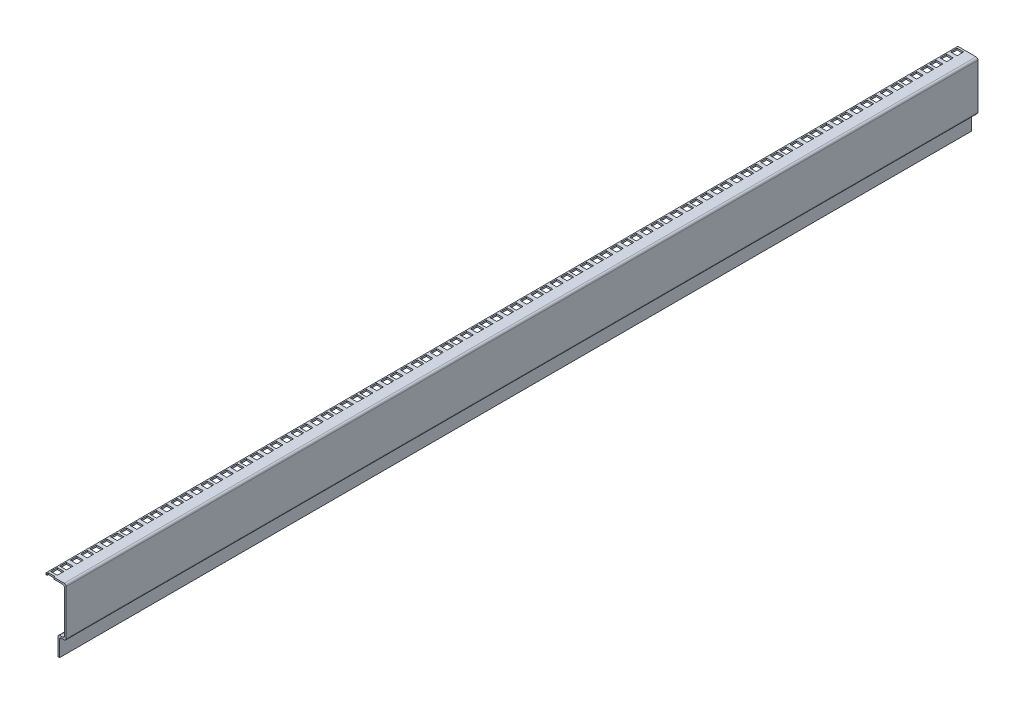
SolidWorks part; units mm, degrees
ref_plane "Front Plane" through (0, 0, 0) normal (0, 0, 1) x (1, 0, 0)
ref_plane "Top Plane" through (0, 0, 0) normal (0, 1, 0) x (1, 0, 0)
ref_plane "Right Plane" through (0, 0, 0) normal (1, 0, 0) x (0, 0, -1)
ref_plane "Plane1" through (-6.8, 0, 0) normal (-1, 0, 0) x (0, -1, 0)
sketch "Sketch1" plane through (-6.8, 0, 0) normal (-1, 0, 0) x (0, -1, 0)
  line L0 (-2.5, -935) -> (99, -935)
  line L1 (99, -935) -> (99, 450.86)
  line L2 (99, 450.86) -> (-2.5, 450.86)
  line L3 (-2.5, 450.86) -> (-2.5, -935)
  dimension "D1" = 101.5
  dimension "D2" = 1385.86
extrude "Boss-Extrude1" add sketch "Sketch1" against normal blind 30.6
sketch "Sketch2" plane through (0, 0, -935) normal (0, 0, -1) x (-1, 0, 0)
  line L0 (6.8, -99) -> (6.8, 0)
  line L1 (6.8, 0) -> (-21.3, 0)
  line L2 (-21.3, 0) -> (-21.3, -99)
  line L3 (-21.3, -99) -> (6.8, -99)
  line L4 (-23.8, 2.5) -> (-23.8, -99) construction
  line L5 (-23.8, 2.5) -> (6.8, 2.5) construction
  line L6 (6.8, 2.5) -> (6.8, -99) construction
  line L7 (-23.8, -99) -> (6.8, -99) construction
  dimension "D1" = 2.5
  dimension "D2" = 2.5
extrude "Cut-Extrude1" cut sketch "Sketch2" against normal through all
sketch "Sketch3" plane through (21.3, 0, 0) normal (-1, 0, 0) x (0, 0, 1)
  line L0 (-935, -99) -> (-935, -69.5)
  line L1 (-935, -69.5) -> (450.86, -69.5)
  line L2 (450.86, -69.5) -> (450.86, -99)
  line L3 (450.86, -99) -> (-935, -99)
  line L4 (-935, 0) -> (-935, -99) construction
  line L5 (450.86, 0) -> (450.86, -99) construction
  line L6 (450.86, -99) -> (-935, -99) construction
  dimension "D1" = 29.5
extrude "Boss-Extrude2" add sketch "Sketch3" along normal blind 10
sketch "Sketch4" plane through (0, 0, 450.86) normal (0, 0, 1) x (1, 0, 0)
  line L0 (23.8, -72) -> (13.8, -72)
  line L1 (13.8, -72) -> (13.8, -99)
  line L2 (13.8, -99) -> (23.8, -99)
  line L3 (23.8, -99) -> (23.8, -72)
  line L4 (11.3, -69.5) -> (21.3, -69.5) construction
  line L5 (11.3, -99) -> (11.3, -69.5) construction
  line L6 (23.8, -99) -> (23.8, 2.5) construction
  line L7 (23.8, -99) -> (11.3, -99) construction
  dimension "D1" = 2.5
  dimension "D2" = 2.5
extrude "Cut-Extrude2" cut sketch "Sketch4" against normal through all
sketch "Sketch5" plane through (0, 2.5, 0) normal (0, 1, 0) x (-1, 0, 0)
  line L0 (-5, 923.15) -> (5, 923.15)
  line L1 (5, 923.15) -> (5, 449.01)
  line L2 (5, 449.01) -> (-5, 449.01)
  line L3 (-5, 449.01) -> (-5, 923.15)
  line L4 (-23.8, 450.86) -> (6.8, 450.86) construction
  line L5 (6.8, 450.86) -> (6.8, -935) construction
  dimension "D1" = 1.85
  dimension "D2" = 1.8
extrude "Cut-Extrude3" cut sketch "Sketch5" against normal through all
sketch "Sketch37" plane through (0, 2.5, 0) normal (0, 1, 0) x (-1, 0, 0)
  line L0 (-5, 435.5463) -> (5, 435.5463)
  line L1 (5, 435.5463) -> (5, 445.5463)
  line L2 (5, 445.5463) -> (-5, 445.5463)
  line L3 (-5, 445.5463) -> (-5, 435.5463)
extrude "Cut-Extrude35" cut sketch "Sketch37" against normal through all
sketch "Sketch38" plane through (0, 2.5, 0) normal (0, 1, 0) x (-1, 0, 0)
  line L0 (-5, 421.711) -> (5, 421.711)
  line L1 (5, 421.711) -> (5, 431.711)
  line L2 (5, 431.711) -> (-5, 431.711)
  line L3 (-5, 431.711) -> (-5, 421.711)
extrude "Cut-Extrude36" cut sketch "Sketch38" against normal through all
sketch "Sketch39" plane through (0, 2.5, 0) normal (0, 1, 0) x (-1, 0, 0)
  line L0 (-5, 405.836) -> (5, 405.836)
  line L1 (5, 405.836) -> (5, 415.836)
  line L2 (5, 415.836) -> (-5, 415.836)
  line L3 (-5, 415.836) -> (-5, 405.836)
extrude "Cut-Extrude37" cut sketch "Sketch39" against normal through all
sketch "Sketch40" plane through (0, 2.5, 0) normal (0, 1, 0) x (-1, 0, 0)
  line L0 (-5, 389.961) -> (5, 389.961)
  line L1 (5, 389.961) -> (5, 399.961)
  line L2 (5, 399.961) -> (-5, 399.961)
  line L3 (-5, 399.961) -> (-5, 389.961)
extrude "Cut-Extrude38" cut sketch "Sketch40" against normal through all
sketch "Sketch41" plane through (0, 2.5, 0) normal (0, 1, 0) x (-1, 0, 0)
  line L0 (-5, 376.1256) -> (5, 376.1256)
  line L1 (5, 376.1256) -> (5, 386.1256)
  line L2 (5, 386.1256) -> (-5, 386.1256)
  line L3 (-5, 386.1256) -> (-5, 376.1256)
extrude "Cut-Extrude39" cut sketch "Sketch41" against normal through all
sketch "Sketch42" plane through (0, 2.5, 0) normal (0, 1, 0) x (-1, 0, 0)
  line L0 (-5, 360.2506) -> (5, 360.2506)
  line L1 (5, 360.2506) -> (5, 370.2506)
  line L2 (5, 370.2506) -> (-5, 370.2506)
  line L3 (-5, 370.2506) -> (-5, 360.2506)
extrude "Cut-Extrude40" cut sketch "Sketch42" against normal through all
sketch "Sketch43" plane through (0, 2.5, 0) normal (0, 1, 0) x (-1, 0, 0)
  line L0 (-5, 344.3756) -> (5, 344.3756)
  line L1 (5, 344.3756) -> (5, 354.3756)
  line L2 (5, 354.3756) -> (-5, 354.3756)
  line L3 (-5, 354.3756) -> (-5, 344.3756)
extrude "Cut-Extrude41" cut sketch "Sketch43" against normal through all
sketch "Sketch44" plane through (0, 2.5, 0) normal (0, 1, 0) x (-1, 0, 0)
  line L0 (-5, 330.5402) -> (5, 330.5402)
  line L1 (5, 330.5402) -> (5, 340.5402)
  line L2 (5, 340.5402) -> (-5, 340.5402)
  line L3 (-5, 340.5402) -> (-5, 330.5402)
extrude "Cut-Extrude42" cut sketch "Sketch44" against normal through all
sketch "Sketch45" plane through (0, 2.5, 0) normal (0, 1, 0) x (-1, 0, 0)
  line L0 (-5, 314.6652) -> (5, 314.6652)
  line L1 (5, 314.6652) -> (5, 324.6652)
  line L2 (5, 324.6652) -> (-5, 324.6652)
  line L3 (-5, 324.6652) -> (-5, 314.6652)
extrude "Cut-Extrude43" cut sketch "Sketch45" against normal through all
sketch "Sketch46" plane through (0, 2.5, 0) normal (0, 1, 0) x (-1, 0, 0)
  line L0 (-5, 298.7902) -> (5, 298.7902)
  line L1 (5, 298.7902) -> (5, 308.7902)
  line L2 (5, 308.7902) -> (-5, 308.7902)
  line L3 (-5, 308.7902) -> (-5, 298.7902)
extrude "Cut-Extrude44" cut sketch "Sketch46" against normal through all
sketch "Sketch47" plane through (0, 2.5, 0) normal (0, 1, 0) x (-1, 0, 0)
  line L0 (-5, 284.9549) -> (5, 284.9549)
  line L1 (5, 284.9549) -> (5, 294.9549)
  line L2 (5, 294.9549) -> (-5, 294.9549)
  line L3 (-5, 294.9549) -> (-5, 284.9549)
extrude "Cut-Extrude45" cut sketch "Sketch47" against normal through all
sketch "Sketch48" plane through (0, 2.5, 0) normal (0, 1, 0) x (-1, 0, 0)
  line L0 (-5, 269.0799) -> (5, 269.0799)
  line L1 (5, 269.0799) -> (5, 279.0799)
  line L2 (5, 279.0799) -> (-5, 279.0799)
  line L3 (-5, 279.0799) -> (-5, 269.0799)
extrude "Cut-Extrude46" cut sketch "Sketch48" against normal through all
sketch "Sketch49" plane through (0, 2.5, 0) normal (0, 1, 0) x (-1, 0, 0)
  line L0 (-5, 253.2049) -> (5, 253.2049)
  line L1 (5, 253.2049) -> (5, 263.2049)
  line L2 (5, 263.2049) -> (-5, 263.2049)
  line L3 (-5, 263.2049) -> (-5, 253.2049)
extrude "Cut-Extrude47" cut sketch "Sketch49" against normal through all
sketch "Sketch50" plane through (0, 2.5, 0) normal (0, 1, 0) x (-1, 0, 0)
  line L0 (-5, 239.3695) -> (5, 239.3695)
  line L1 (5, 239.3695) -> (5, 249.3695)
  line L2 (5, 249.3695) -> (-5, 249.3695)
  line L3 (-5, 249.3695) -> (-5, 239.3695)
extrude "Cut-Extrude48" cut sketch "Sketch50" against normal through all
sketch "Sketch51" plane through (0, 2.5, 0) normal (0, 1, 0) x (-1, 0, 0)
  line L0 (-5, 223.4945) -> (5, 223.4945)
  line L1 (5, 223.4945) -> (5, 233.4945)
  line L2 (5, 233.4945) -> (-5, 233.4945)
  line L3 (-5, 233.4945) -> (-5, 223.4945)
extrude "Cut-Extrude49" cut sketch "Sketch51" against normal through all
sketch "Sketch52" plane through (0, 2.5, 0) normal (0, 1, 0) x (-1, 0, 0)
  line L0 (-5, 207.6195) -> (5, 207.6195)
  line L1 (5, 207.6195) -> (5, 217.6195)
  line L2 (5, 217.6195) -> (-5, 217.6195)
  line L3 (-5, 217.6195) -> (-5, 207.6195)
extrude "Cut-Extrude50" cut sketch "Sketch52" against normal through all
sketch "Sketch53" plane through (0, 2.5, 0) normal (0, 1, 0) x (-1, 0, 0)
  line L0 (-5, 193.7841) -> (5, 193.7841)
  line L1 (5, 193.7841) -> (5, 203.7841)
  line L2 (5, 203.7841) -> (-5, 203.7841)
  line L3 (-5, 203.7841) -> (-5, 193.7841)
extrude "Cut-Extrude51" cut sketch "Sketch53" against normal through all
sketch "Sketch54" plane through (0, 2.5, 0) normal (0, 1, 0) x (-1, 0, 0)
  line L0 (-5, 177.9091) -> (5, 177.9091)
  line L1 (5, 177.9091) -> (5, 187.9091)
  line L2 (5, 187.9091) -> (-5, 187.9091)
  line L3 (-5, 187.9091) -> (-5, 177.9091)
extrude "Cut-Extrude52" cut sketch "Sketch54" against normal through all
sketch "Sketch55" plane through (0, 2.5, 0) normal (0, 1, 0) x (-1, 0, 0)
  line L0 (-5, 162.0341) -> (5, 162.0341)
  line L1 (5, 162.0341) -> (5, 172.0341)
  line L2 (5, 172.0341) -> (-5, 172.0341)
  line L3 (-5, 172.0341) -> (-5, 162.0341)
extrude "Cut-Extrude53" cut sketch "Sketch55" against normal through all
sketch "Sketch56" plane through (0, 2.5, 0) normal (0, 1, 0) x (-1, 0, 0)
  line L0 (-5, 148.1988) -> (5, 148.1988)
  line L1 (5, 148.1988) -> (5, 158.1988)
  line L2 (5, 158.1988) -> (-5, 158.1988)
  line L3 (-5, 158.1988) -> (-5, 148.1988)
extrude "Cut-Extrude54" cut sketch "Sketch56" against normal through all
sketch "Sketch57" plane through (0, 2.5, 0) normal (0, 1, 0) x (-1, 0, 0)
  line L0 (-5, 132.3238) -> (5, 132.3238)
  line L1 (5, 132.3238) -> (5, 142.3238)
  line L2 (5, 142.3238) -> (-5, 142.3238)
  line L3 (-5, 142.3238) -> (-5, 132.3238)
extrude "Cut-Extrude55" cut sketch "Sketch57" against normal through all
sketch "Sketch58" plane through (0, 2.5, 0) normal (0, 1, 0) x (-1, 0, 0)
  line L0 (-5, 116.4488) -> (5, 116.4488)
  line L1 (5, 116.4488) -> (5, 126.4488)
  line L2 (5, 126.4488) -> (-5, 126.4488)
  line L3 (-5, 126.4488) -> (-5, 116.4488)
extrude "Cut-Extrude56" cut sketch "Sketch58" against normal through all
sketch "Sketch59" plane through (0, 2.5, 0) normal (0, 1, 0) x (-1, 0, 0)
  line L0 (-5, 102.6134) -> (5, 102.6134)
  line L1 (5, 102.6134) -> (5, 112.6134)
  line L2 (5, 112.6134) -> (-5, 112.6134)
  line L3 (-5, 112.6134) -> (-5, 102.6134)
extrude "Cut-Extrude57" cut sketch "Sketch59" against normal through all
sketch "Sketch60" plane through (0, 2.5, 0) normal (0, 1, 0) x (-1, 0, 0)
  line L0 (-5, 86.7384) -> (5, 86.7384)
  line L1 (5, 86.7384) -> (5, 96.7384)
  line L2 (5, 96.7384) -> (-5, 96.7384)
  line L3 (-5, 96.7384) -> (-5, 86.7384)
extrude "Cut-Extrude58" cut sketch "Sketch60" against normal through all
sketch "Sketch61" plane through (0, 2.5, 0) normal (0, 1, 0) x (-1, 0, 0)
  line L0 (-5, 70.8634) -> (5, 70.8634)
  line L1 (5, 70.8634) -> (5, 80.8634)
  line L2 (5, 80.8634) -> (-5, 80.8634)
  line L3 (-5, 80.8634) -> (-5, 70.8634)
extrude "Cut-Extrude59" cut sketch "Sketch61" against normal through all
sketch "Sketch62" plane through (0, 2.5, 0) normal (0, 1, 0) x (-1, 0, 0)
  line L0 (-5, 57.028) -> (5, 57.028)
  line L1 (5, 57.028) -> (5, 67.028)
  line L2 (5, 67.028) -> (-5, 67.028)
  line L3 (-5, 67.028) -> (-5, 57.028)
extrude "Cut-Extrude60" cut sketch "Sketch62" against normal through all
sketch "Sketch63" plane through (0, 2.5, 0) normal (0, 1, 0) x (-1, 0, 0)
  line L0 (-5, 41.153) -> (5, 41.153)
  line L1 (5, 41.153) -> (5, 51.153)
  line L2 (5, 51.153) -> (-5, 51.153)
  line L3 (-5, 51.153) -> (-5, 41.153)
extrude "Cut-Extrude61" cut sketch "Sketch63" against normal through all
sketch "Sketch64" plane through (0, 2.5, 0) normal (0, 1, 0) x (-1, 0, 0)
  line L0 (-5, 25.278) -> (5, 25.278)
  line L1 (5, 25.278) -> (5, 35.278)
  line L2 (5, 35.278) -> (-5, 35.278)
  line L3 (-5, 35.278) -> (-5, 25.278)
extrude "Cut-Extrude62" cut sketch "Sketch64" against normal through all
sketch "Sketch65" plane through (0, 2.5, 0) normal (0, 1, 0) x (-1, 0, 0)
  line L0 (-5, 11.4427) -> (5, 11.4427)
  line L1 (5, 11.4427) -> (5, 21.4427)
  line L2 (5, 21.4427) -> (-5, 21.4427)
  line L3 (-5, 21.4427) -> (-5, 11.4427)
extrude "Cut-Extrude63" cut sketch "Sketch65" against normal through all
sketch "Sketch66" plane through (0, 2.5, 0) normal (0, 1, 0) x (-1, 0, 0)
  line L0 (-5, -4.4323) -> (5, -4.4323)
  line L1 (5, -4.4323) -> (5, 5.5677)
  line L2 (5, 5.5677) -> (-5, 5.5677)
  line L3 (-5, 5.5677) -> (-5, -4.4323)
extrude "Cut-Extrude64" cut sketch "Sketch66" against normal through all
sketch "Sketch67" plane through (0, 2.5, 0) normal (0, 1, 0) x (-1, 0, 0)
  line L0 (-5, -34.1427) -> (5, -34.1427)
  line L1 (5, -34.1427) -> (5, -24.1427)
  line L2 (5, -24.1427) -> (-5, -24.1427)
  line L3 (-5, -24.1427) -> (-5, -34.1427)
extrude "Cut-Extrude65" cut sketch "Sketch67" against normal through all
sketch "Sketch68" plane through (0, 2.5, 0) normal (0, 1, 0) x (-1, 0, 0)
  line L0 (-5, -50.0177) -> (5, -50.0177)
  line L1 (5, -50.0177) -> (5, -40.0177)
  line L2 (5, -40.0177) -> (-5, -40.0177)
  line L3 (-5, -40.0177) -> (-5, -50.0177)
extrude "Cut-Extrude66" cut sketch "Sketch68" against normal through all
sketch "Sketch69" plane through (0, 2.5, 0) normal (0, 1, 0) x (-1, 0, 0)
  line L0 (-5, -65.8927) -> (5, -65.8927)
  line L1 (5, -65.8927) -> (5, -55.8927)
  line L2 (5, -55.8927) -> (-5, -55.8927)
  line L3 (-5, -55.8927) -> (-5, -65.8927)
extrude "Cut-Extrude67" cut sketch "Sketch69" against normal through all
sketch "Sketch70" plane through (0, 2.5, 0) normal (0, 1, 0) x (-1, 0, 0)
  line L0 (-5, -79.728) -> (5, -79.728)
  line L1 (5, -79.728) -> (5, -69.728)
  line L2 (5, -69.728) -> (-5, -69.728)
  line L3 (-5, -69.728) -> (-5, -79.728)
extrude "Cut-Extrude68" cut sketch "Sketch70" against normal through all
sketch "Sketch71" plane through (0, 2.5, 0) normal (0, 1, 0) x (-1, 0, 0)
  line L0 (-5, -95.603) -> (5, -95.603)
  line L1 (5, -95.603) -> (5, -85.603)
  line L2 (5, -85.603) -> (-5, -85.603)
  line L3 (-5, -85.603) -> (-5, -95.603)
extrude "Cut-Extrude69" cut sketch "Sketch71" against normal through all
sketch "Sketch72" plane through (0, 2.5, 0) normal (0, 1, 0) x (-1, 0, 0)
  line L0 (-5, -111.478) -> (5, -111.478)
  line L1 (5, -111.478) -> (5, -101.478)
  line L2 (5, -101.478) -> (-5, -101.478)
  line L3 (-5, -101.478) -> (-5, -111.478)
extrude "Cut-Extrude70" cut sketch "Sketch72" against normal through all
sketch "Sketch73" plane through (0, 2.5, 0) normal (0, 1, 0) x (-1, 0, 0)
  line L0 (-5, -125.3134) -> (5, -125.3134)
  line L1 (5, -125.3134) -> (5, -115.3134)
  line L2 (5, -115.3134) -> (-5, -115.3134)
  line L3 (-5, -115.3134) -> (-5, -125.3134)
extrude "Cut-Extrude71" cut sketch "Sketch73" against normal through all
sketch "Sketch74" plane through (0, 2.5, 0) normal (0, 1, 0) x (-1, 0, 0)
  line L0 (-5, -141.1884) -> (5, -141.1884)
  line L1 (5, -141.1884) -> (5, -131.1884)
  line L2 (5, -131.1884) -> (-5, -131.1884)
  line L3 (-5, -131.1884) -> (-5, -141.1884)
extrude "Cut-Extrude72" cut sketch "Sketch74" against normal through all
sketch "Sketch75" plane through (0, 2.5, 0) normal (0, 1, 0) x (-1, 0, 0)
  line L0 (-5, -157.0634) -> (5, -157.0634)
  line L1 (5, -157.0634) -> (5, -147.0634)
  line L2 (5, -147.0634) -> (-5, -147.0634)
  line L3 (-5, -147.0634) -> (-5, -157.0634)
extrude "Cut-Extrude73" cut sketch "Sketch75" against normal through all
sketch "Sketch76" plane through (0, 2.5, 0) normal (0, 1, 0) x (-1, 0, 0)
  line L0 (-5, -170.8988) -> (5, -170.8988)
  line L1 (5, -170.8988) -> (5, -160.8988)
  line L2 (5, -160.8988) -> (-5, -160.8988)
  line L3 (-5, -160.8988) -> (-5, -170.8988)
extrude "Cut-Extrude74" cut sketch "Sketch76" against normal through all
sketch "Sketch77" plane through (0, 2.5, 0) normal (0, 1, 0) x (-1, 0, 0)
  line L0 (-5, -186.7738) -> (5, -186.7738)
  line L1 (5, -186.7738) -> (5, -176.7738)
  line L2 (5, -176.7738) -> (-5, -176.7738)
  line L3 (-5, -176.7738) -> (-5, -186.7738)
extrude "Cut-Extrude75" cut sketch "Sketch77" against normal through all
sketch "Sketch78" plane through (0, 2.5, 0) normal (0, 1, 0) x (-1, 0, 0)
  line L0 (-5, -202.6488) -> (5, -202.6488)
  line L1 (5, -202.6488) -> (5, -192.6488)
  line L2 (5, -192.6488) -> (-5, -192.6488)
  line L3 (-5, -192.6488) -> (-5, -202.6488)
extrude "Cut-Extrude76" cut sketch "Sketch78" against normal through all
sketch "Sketch79" plane through (0, 2.5, 0) normal (0, 1, 0) x (-1, 0, 0)
  line L0 (-5, -216.4841) -> (5, -216.4841)
  line L1 (5, -216.4841) -> (5, -206.4841)
  line L2 (5, -206.4841) -> (-5, -206.4841)
  line L3 (-5, -206.4841) -> (-5, -216.4841)
extrude "Cut-Extrude77" cut sketch "Sketch79" against normal through all
sketch "Sketch80" plane through (0, 2.5, 0) normal (0, 1, 0) x (-1, 0, 0)
  line L0 (-5, -232.3591) -> (5, -232.3591)
  line L1 (5, -232.3591) -> (5, -222.3591)
  line L2 (5, -222.3591) -> (-5, -222.3591)
  line L3 (-5, -222.3591) -> (-5, -232.3591)
extrude "Cut-Extrude78" cut sketch "Sketch80" against normal through all
sketch "Sketch81" plane through (0, 2.5, 0) normal (0, 1, 0) x (-1, 0, 0)
  line L0 (-5, -248.2341) -> (5, -248.2341)
  line L1 (5, -248.2341) -> (5, -238.2341)
  line L2 (5, -238.2341) -> (-5, -238.2341)
  line L3 (-5, -238.2341) -> (-5, -248.2341)
extrude "Cut-Extrude79" cut sketch "Sketch81" against normal through all
sketch "Sketch82" plane through (0, 2.5, 0) normal (0, 1, 0) x (-1, 0, 0)
  line L0 (-5, -262.0695) -> (5, -262.0695)
  line L1 (5, -262.0695) -> (5, -252.0695)
  line L2 (5, -252.0695) -> (-5, -252.0695)
  line L3 (-5, -252.0695) -> (-5, -262.0695)
extrude "Cut-Extrude80" cut sketch "Sketch82" against normal through all
sketch "Sketch83" plane through (0, 2.5, 0) normal (0, 1, 0) x (-1, 0, 0)
  line L0 (-5, -277.9445) -> (5, -277.9445)
  line L1 (5, -277.9445) -> (5, -267.9445)
  line L2 (5, -267.9445) -> (-5, -267.9445)
  line L3 (-5, -267.9445) -> (-5, -277.9445)
extrude "Cut-Extrude81" cut sketch "Sketch83" against normal through all
sketch "Sketch84" plane through (0, 2.5, 0) normal (0, 1, 0) x (-1, 0, 0)
  line L0 (-5, -293.8195) -> (5, -293.8195)
  line L1 (5, -293.8195) -> (5, -283.8195)
  line L2 (5, -283.8195) -> (-5, -283.8195)
  line L3 (-5, -283.8195) -> (-5, -293.8195)
extrude "Cut-Extrude82" cut sketch "Sketch84" against normal through all
sketch "Sketch85" plane through (0, 2.5, 0) normal (0, 1, 0) x (-1, 0, 0)
  line L0 (-5, -307.6549) -> (5, -307.6549)
  line L1 (5, -307.6549) -> (5, -297.6549)
  line L2 (5, -297.6549) -> (-5, -297.6549)
  line L3 (-5, -297.6549) -> (-5, -307.6549)
extrude "Cut-Extrude83" cut sketch "Sketch85" against normal through all
sketch "Sketch86" plane through (0, 2.5, 0) normal (0, 1, 0) x (-1, 0, 0)
  line L0 (-5, -323.5299) -> (5, -323.5299)
  line L1 (5, -323.5299) -> (5, -313.5299)
  line L2 (5, -313.5299) -> (-5, -313.5299)
  line L3 (-5, -313.5299) -> (-5, -323.5299)
extrude "Cut-Extrude84" cut sketch "Sketch86" against normal through all
sketch "Sketch87" plane through (0, 2.5, 0) normal (0, 1, 0) x (-1, 0, 0)
  line L0 (-5, -339.4049) -> (5, -339.4049)
  line L1 (5, -339.4049) -> (5, -329.4049)
  line L2 (5, -329.4049) -> (-5, -329.4049)
  line L3 (-5, -329.4049) -> (-5, -339.4049)
extrude "Cut-Extrude85" cut sketch "Sketch87" against normal through all
sketch "Sketch88" plane through (0, 2.5, 0) normal (0, 1, 0) x (-1, 0, 0)
  line L0 (-5, -353.2402) -> (5, -353.2402)
  line L1 (5, -353.2402) -> (5, -343.2402)
  line L2 (5, -343.2402) -> (-5, -343.2402)
  line L3 (-5, -343.2402) -> (-5, -353.2402)
extrude "Cut-Extrude86" cut sketch "Sketch88" against normal through all
sketch "Sketch89" plane through (0, 2.5, 0) normal (0, 1, 0) x (-1, 0, 0)
  line L0 (-5, -369.1152) -> (5, -369.1152)
  line L1 (5, -369.1152) -> (5, -359.1152)
  line L2 (5, -359.1152) -> (-5, -359.1152)
  line L3 (-5, -359.1152) -> (-5, -369.1152)
extrude "Cut-Extrude87" cut sketch "Sketch89" against normal through all
sketch "Sketch90" plane through (0, 2.5, 0) normal (0, 1, 0) x (-1, 0, 0)
  line L0 (-5, -384.9902) -> (5, -384.9902)
  line L1 (5, -384.9902) -> (5, -374.9902)
  line L2 (5, -374.9902) -> (-5, -374.9902)
  line L3 (-5, -374.9902) -> (-5, -384.9902)
extrude "Cut-Extrude88" cut sketch "Sketch90" against normal through all
sketch "Sketch91" plane through (0, 2.5, 0) normal (0, 1, 0) x (-1, 0, 0)
  line L0 (-5, -398.8256) -> (5, -398.8256)
  line L1 (5, -398.8256) -> (5, -388.8256)
  line L2 (5, -388.8256) -> (-5, -388.8256)
  line L3 (-5, -388.8256) -> (-5, -398.8256)
extrude "Cut-Extrude89" cut sketch "Sketch91" against normal through all
sketch "Sketch92" plane through (0, 2.5, 0) normal (0, 1, 0) x (-1, 0, 0)
  line L0 (-5, -414.7006) -> (5, -414.7006)
  line L1 (5, -414.7006) -> (5, -404.7006)
  line L2 (5, -404.7006) -> (-5, -404.7006)
  line L3 (-5, -404.7006) -> (-5, -414.7006)
extrude "Cut-Extrude90" cut sketch "Sketch92" against normal through all
sketch "Sketch93" plane through (0, 2.5, 0) normal (0, 1, 0) x (-1, 0, 0)
  line L0 (-5, -430.5756) -> (5, -430.5756)
  line L1 (5, -430.5756) -> (5, -420.5756)
  line L2 (5, -420.5756) -> (-5, -420.5756)
  line L3 (-5, -420.5756) -> (-5, -430.5756)
extrude "Cut-Extrude91" cut sketch "Sketch93" against normal through all
sketch "Sketch94" plane through (0, 2.5, 0) normal (0, 1, 0) x (-1, 0, 0)
  line L0 (-5, -444.411) -> (5, -444.411)
  line L1 (5, -444.411) -> (5, -434.411)
  line L2 (5, -434.411) -> (-5, -434.411)
  line L3 (-5, -434.411) -> (-5, -444.411)
extrude "Cut-Extrude92" cut sketch "Sketch94" against normal through all
sketch "Sketch95" plane through (0, 2.5, 0) normal (0, 1, 0) x (-1, 0, 0)
  line L0 (-5, -460.286) -> (5, -460.286)
  line L1 (5, -460.286) -> (5, -450.286)
  line L2 (5, -450.286) -> (-5, -450.286)
  line L3 (-5, -450.286) -> (-5, -460.286)
extrude "Cut-Extrude93" cut sketch "Sketch95" against normal through all
sketch "Sketch96" plane through (0, 2.5, 0) normal (0, 1, 0) x (-1, 0, 0)
  line L0 (-5, -476.161) -> (5, -476.161)
  line L1 (5, -476.161) -> (5, -466.161)
  line L2 (5, -466.161) -> (-5, -466.161)
  line L3 (-5, -466.161) -> (-5, -476.161)
extrude "Cut-Extrude94" cut sketch "Sketch96" against normal through all
sketch "Sketch97" plane through (0, 2.5, 0) normal (0, 1, 0) x (-1, 0, 0)
  line L0 (-5, -489.9963) -> (5, -489.9963)
  line L1 (5, -489.9963) -> (5, -479.9963)
  line L2 (5, -479.9963) -> (-5, -479.9963)
  line L3 (-5, -479.9963) -> (-5, -489.9963)
extrude "Cut-Extrude95" cut sketch "Sketch97" against normal through all
sketch "Sketch98" plane through (0, 2.5, 0) normal (0, 1, 0) x (-1, 0, 0)
  line L0 (-5, -505.8713) -> (5, -505.8713)
  line L1 (5, -505.8713) -> (5, -495.8713)
  line L2 (5, -495.8713) -> (-5, -495.8713)
  line L3 (-5, -495.8713) -> (-5, -505.8713)
extrude "Cut-Extrude96" cut sketch "Sketch98" against normal through all
sketch "Sketch99" plane through (0, 2.5, 0) normal (0, 1, 0) x (-1, 0, 0)
  line L0 (-5, -521.7463) -> (5, -521.7463)
  line L1 (5, -521.7463) -> (5, -511.7463)
  line L2 (5, -511.7463) -> (-5, -511.7463)
  line L3 (-5, -511.7463) -> (-5, -521.7463)
extrude "Cut-Extrude97" cut sketch "Sketch99" against normal through all
sketch "Sketch100" plane through (0, 2.5, 0) normal (0, 1, 0) x (-1, 0, 0)
  line L0 (-5, -535.5817) -> (5, -535.5817)
  line L1 (5, -535.5817) -> (5, -525.5817)
  line L2 (5, -525.5817) -> (-5, -525.5817)
  line L3 (-5, -525.5817) -> (-5, -535.5817)
extrude "Cut-Extrude98" cut sketch "Sketch100" against normal through all
sketch "Sketch101" plane through (0, 2.5, 0) normal (0, 1, 0) x (-1, 0, 0)
  line L0 (-5, -551.4567) -> (5, -551.4567)
  line L1 (5, -551.4567) -> (5, -541.4567)
  line L2 (5, -541.4567) -> (-5, -541.4567)
  line L3 (-5, -541.4567) -> (-5, -551.4567)
extrude "Cut-Extrude99" cut sketch "Sketch101" against normal through all
sketch "Sketch102" plane through (0, 2.5, 0) normal (0, 1, 0) x (-1, 0, 0)
  line L0 (-5, -567.3317) -> (5, -567.3317)
  line L1 (5, -567.3317) -> (5, -557.3317)
  line L2 (5, -557.3317) -> (-5, -557.3317)
  line L3 (-5, -557.3317) -> (-5, -567.3317)
extrude "Cut-Extrude100" cut sketch "Sketch102" against normal through all
sketch "Sketch103" plane through (0, 2.5, 0) normal (0, 1, 0) x (-1, 0, 0)
  line L0 (-5, -581.1671) -> (5, -581.1671)
  line L1 (5, -581.1671) -> (5, -571.1671)
  line L2 (5, -571.1671) -> (-5, -571.1671)
  line L3 (-5, -571.1671) -> (-5, -581.1671)
extrude "Cut-Extrude101" cut sketch "Sketch103" against normal through all
sketch "Sketch104" plane through (0, 2.5, 0) normal (0, 1, 0) x (-1, 0, 0)
  line L0 (-5, -597.0421) -> (5, -597.0421)
  line L1 (5, -597.0421) -> (5, -587.0421)
  line L2 (5, -587.0421) -> (-5, -587.0421)
  line L3 (-5, -587.0421) -> (-5, -597.0421)
extrude "Cut-Extrude102" cut sketch "Sketch104" against normal through all
sketch "Sketch105" plane through (0, 2.5, 0) normal (0, 1, 0) x (-1, 0, 0)
  line L0 (-5, -612.9171) -> (5, -612.9171)
  line L1 (5, -612.9171) -> (5, -602.9171)
  line L2 (5, -602.9171) -> (-5, -602.9171)
  line L3 (-5, -602.9171) -> (-5, -612.9171)
extrude "Cut-Extrude103" cut sketch "Sketch105" against normal through all
sketch "Sketch106" plane through (0, 2.5, 0) normal (0, 1, 0) x (-1, 0, 0)
  line L0 (-5, -626.7524) -> (5, -626.7524)
  line L1 (5, -626.7524) -> (5, -616.7524)
  line L2 (5, -616.7524) -> (-5, -616.7524)
  line L3 (-5, -616.7524) -> (-5, -626.7524)
extrude "Cut-Extrude104" cut sketch "Sketch106" against normal through all
sketch "Sketch107" plane through (0, 2.5, 0) normal (0, 1, 0) x (-1, 0, 0)
  line L0 (-5, -642.6274) -> (5, -642.6274)
  line L1 (5, -642.6274) -> (5, -632.6274)
  line L2 (5, -632.6274) -> (-5, -632.6274)
  line L3 (-5, -632.6274) -> (-5, -642.6274)
extrude "Cut-Extrude105" cut sketch "Sketch107" against normal through all
sketch "Sketch108" plane through (0, 2.5, 0) normal (0, 1, 0) x (-1, 0, 0)
  line L0 (-5, -658.5024) -> (5, -658.5024)
  line L1 (5, -658.5024) -> (5, -648.5024)
  line L2 (5, -648.5024) -> (-5, -648.5024)
  line L3 (-5, -648.5024) -> (-5, -658.5024)
extrude "Cut-Extrude106" cut sketch "Sketch108" against normal through all
sketch "Sketch109" plane through (0, 2.5, 0) normal (0, 1, 0) x (-1, 0, 0)
  line L0 (-5, -672.3378) -> (5, -672.3378)
  line L1 (5, -672.3378) -> (5, -662.3378)
  line L2 (5, -662.3378) -> (-5, -662.3378)
  line L3 (-5, -662.3378) -> (-5, -672.3378)
extrude "Cut-Extrude107" cut sketch "Sketch109" against normal through all
sketch "Sketch110" plane through (0, 2.5, 0) normal (0, 1, 0) x (-1, 0, 0)
  line L0 (-5, -688.2128) -> (5, -688.2128)
  line L1 (5, -688.2128) -> (5, -678.2128)
  line L2 (5, -678.2128) -> (-5, -678.2128)
  line L3 (-5, -678.2128) -> (-5, -688.2128)
extrude "Cut-Extrude108" cut sketch "Sketch110" against normal through all
sketch "Sketch111" plane through (0, 2.5, 0) normal (0, 1, 0) x (-1, 0, 0)
  line L0 (-5, -704.0878) -> (5, -704.0878)
  line L1 (5, -704.0878) -> (5, -694.0878)
  line L2 (5, -694.0878) -> (-5, -694.0878)
  line L3 (-5, -694.0878) -> (-5, -704.0878)
extrude "Cut-Extrude109" cut sketch "Sketch111" against normal through all
sketch "Sketch112" plane through (0, 2.5, 0) normal (0, 1, 0) x (-1, 0, 0)
  line L0 (-5, -717.9232) -> (5, -717.9232)
  line L1 (5, -717.9232) -> (5, -707.9232)
  line L2 (5, -707.9232) -> (-5, -707.9232)
  line L3 (-5, -707.9232) -> (-5, -717.9232)
extrude "Cut-Extrude110" cut sketch "Sketch112" against normal through all
sketch "Sketch113" plane through (0, 2.5, 0) normal (0, 1, 0) x (-1, 0, 0)
  line L0 (-5, -733.7982) -> (5, -733.7982)
  line L1 (5, -733.7982) -> (5, -723.7982)
  line L2 (5, -723.7982) -> (-5, -723.7982)
  line L3 (-5, -723.7982) -> (-5, -733.7982)
extrude "Cut-Extrude111" cut sketch "Sketch113" against normal through all
sketch "Sketch114" plane through (0, 2.5, 0) normal (0, 1, 0) x (-1, 0, 0)
  line L0 (-5, -749.6732) -> (5, -749.6732)
  line L1 (5, -749.6732) -> (5, -739.6732)
  line L2 (5, -739.6732) -> (-5, -739.6732)
  line L3 (-5, -739.6732) -> (-5, -749.6732)
extrude "Cut-Extrude112" cut sketch "Sketch114" against normal through all
sketch "Sketch115" plane through (0, 2.5, 0) normal (0, 1, 0) x (-1, 0, 0)
  line L0 (-5, -763.5085) -> (5, -763.5085)
  line L1 (5, -763.5085) -> (5, -753.5085)
  line L2 (5, -753.5085) -> (-5, -753.5085)
  line L3 (-5, -753.5085) -> (-5, -763.5085)
extrude "Cut-Extrude113" cut sketch "Sketch115" against normal through all
sketch "Sketch116" plane through (0, 2.5, 0) normal (0, 1, 0) x (-1, 0, 0)
  line L0 (-5, -779.3835) -> (5, -779.3835)
  line L1 (5, -779.3835) -> (5, -769.3835)
  line L2 (5, -769.3835) -> (-5, -769.3835)
  line L3 (-5, -769.3835) -> (-5, -779.3835)
extrude "Cut-Extrude114" cut sketch "Sketch116" against normal through all
sketch "Sketch117" plane through (0, 2.5, 0) normal (0, 1, 0) x (-1, 0, 0)
  line L0 (-5, -795.2585) -> (5, -795.2585)
  line L1 (5, -795.2585) -> (5, -785.2585)
  line L2 (5, -785.2585) -> (-5, -785.2585)
  line L3 (-5, -785.2585) -> (-5, -795.2585)
extrude "Cut-Extrude115" cut sketch "Sketch117" against normal through all
sketch "Sketch118" plane through (0, 2.5, 0) normal (0, 1, 0) x (-1, 0, 0)
  line L0 (-5, -809.0939) -> (5, -809.0939)
  line L1 (5, -809.0939) -> (5, -799.0939)
  line L2 (5, -799.0939) -> (-5, -799.0939)
  line L3 (-5, -799.0939) -> (-5, -809.0939)
extrude "Cut-Extrude116" cut sketch "Sketch118" against normal through all
sketch "Sketch119" plane through (0, 2.5, 0) normal (0, 1, 0) x (-1, 0, 0)
  line L0 (-5, -824.9689) -> (5, -824.9689)
  line L1 (5, -824.9689) -> (5, -814.9689)
  line L2 (5, -814.9689) -> (-5, -814.9689)
  line L3 (-5, -814.9689) -> (-5, -824.9689)
extrude "Cut-Extrude117" cut sketch "Sketch119" against normal through all
sketch "Sketch120" plane through (0, 2.5, 0) normal (0, 1, 0) x (-1, 0, 0)
  line L0 (-5, -840.8439) -> (5, -840.8439)
  line L1 (5, -840.8439) -> (5, -830.8439)
  line L2 (5, -830.8439) -> (-5, -830.8439)
  line L3 (-5, -830.8439) -> (-5, -840.8439)
extrude "Cut-Extrude118" cut sketch "Sketch120" against normal through all
sketch "Sketch121" plane through (0, 2.5, 0) normal (0, 1, 0) x (-1, 0, 0)
  line L0 (-5, -854.6793) -> (5, -854.6793)
  line L1 (5, -854.6793) -> (5, -844.6793)
  line L2 (5, -844.6793) -> (-5, -844.6793)
  line L3 (-5, -844.6793) -> (-5, -854.6793)
extrude "Cut-Extrude119" cut sketch "Sketch121" against normal through all
sketch "Sketch122" plane through (0, 2.5, 0) normal (0, 1, 0) x (-1, 0, 0)
  line L0 (-5, -870.5543) -> (5, -870.5543)
  line L1 (5, -870.5543) -> (5, -860.5543)
  line L2 (5, -860.5543) -> (-5, -860.5543)
  line L3 (-5, -860.5543) -> (-5, -870.5543)
extrude "Cut-Extrude120" cut sketch "Sketch122" against normal through all
sketch "Sketch123" plane through (0, 2.5, 0) normal (0, 1, 0) x (-1, 0, 0)
  line L0 (-5, -886.4293) -> (5, -886.4293)
  line L1 (5, -886.4293) -> (5, -876.4293)
  line L2 (5, -876.4293) -> (-5, -876.4293)
  line L3 (-5, -876.4293) -> (-5, -886.4293)
extrude "Cut-Extrude121" cut sketch "Sketch123" against normal through all
sketch "Sketch124" plane through (0, 2.5, 0) normal (0, 1, 0) x (-1, 0, 0)
  line L0 (-5, -900.2646) -> (5, -900.2646)
  line L1 (5, -900.2646) -> (5, -890.2646)
  line L2 (5, -890.2646) -> (-5, -890.2646)
  line L3 (-5, -890.2646) -> (-5, -900.2646)
extrude "Cut-Extrude122" cut sketch "Sketch124" against normal through all
sketch "Sketch125" plane through (0, 2.5, 0) normal (0, 1, 0) x (-1, 0, 0)
  line L0 (-5, -916.1396) -> (5, -916.1396)
  line L1 (5, -916.1396) -> (5, -906.1396)
  line L2 (5, -906.1396) -> (-5, -906.1396)
  line L3 (-5, -906.1396) -> (-5, -916.1396)
extrude "Cut-Extrude123" cut sketch "Sketch125" against normal through all
sketch "Sketch126" plane through (0, 2.5, 0) normal (0, 1, 0) x (-1, 0, 0)
  line L0 (-5, -932.0146) -> (5, -932.0146)
  line L1 (5, -932.0146) -> (5, -922.0146)
  line L2 (5, -922.0146) -> (-5, -922.0146)
  line L3 (-5, -922.0146) -> (-5, -932.0146)
extrude "Cut-Extrude124" cut sketch "Sketch126" against normal through all
sketch "Sketch127" plane through (0, 0, 0) normal (0, -1, 0) x (1, 0, 0)
  line L0 (-5, -20.3073) -> (5, -20.3073)
  line L1 (5, -20.3073) -> (5, -10.3073)
  line L2 (5, -10.3073) -> (-5, -10.3073)
  line L3 (-5, -10.3073) -> (-5, -20.3073)
extrude "Cut-Extrude125" cut sketch "Sketch127" against normal through all
fillet "Fillet1" radius 3 6 edges at (13.8, -72, -242.07) (11.3, -69.5, -242.07) (21.3, -69.5, -242.07) (23.8, -72, -242.07) (23.8, 2.5, -242.07) (21.3, 0, -242.07) tangent propagation no
